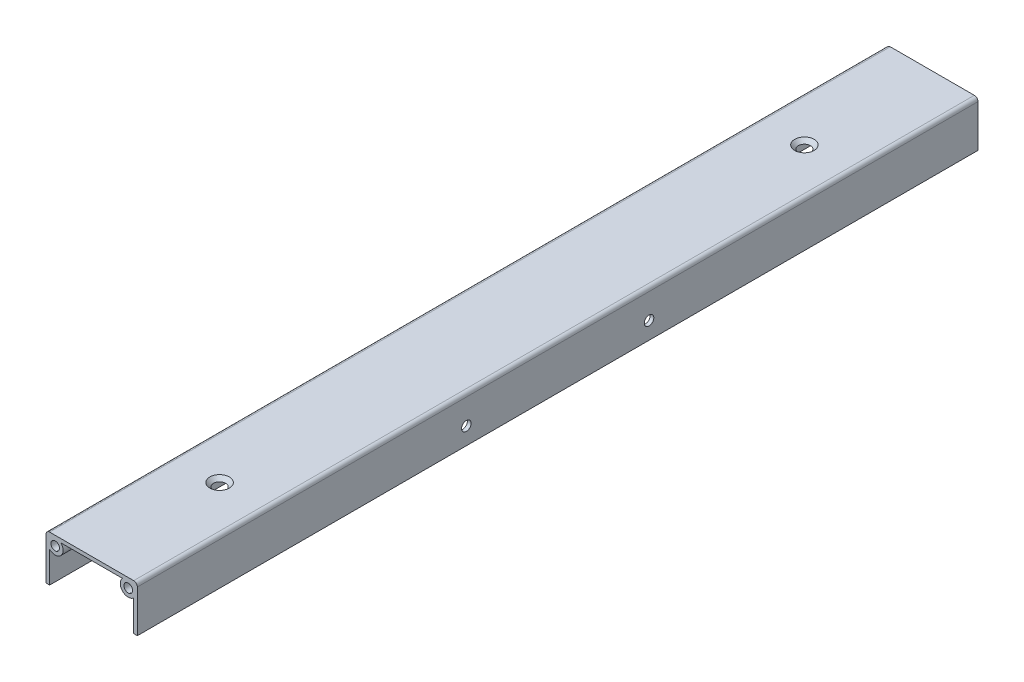
SolidWorks part; units mm, degrees
ref_plane "Front Plane" through (0, 0, 0) normal (0, 0, 1) x (1, 0, 0)
ref_plane "Top Plane" through (0, 0, 0) normal (0, 1, 0) x (1, 0, 0)
ref_plane "Right Plane" through (0, 0, 0) normal (1, 0, 0) x (0, 0, -1)
sketch "Sketch1" plane through (0, 0, 0) normal (0, 0, 1) x (1, 0, 0)
  line L0 (0, 31.75) -> (0, -31.75) construction
  line L1 (-31.75, -31.75) -> (31.75, -31.75)
  line L2 (-31.75, -31.75) -> (-31.75, 31.75)
  line L3 (-31.75, 31.75) -> (31.75, 31.75)
  line L4 (31.75, -31.75) -> (31.75, 31.75)
  line L5 (-31.75, -31.75) -> (31.75, 31.75) construction
  line L6 (-31.75, 31.75) -> (31.75, -31.75) construction
  line L7 (-31.75, 0) -> (31.75, 0) construction
  circle A0 centre (-25.4, 25.4) radius 3
  circle A1 centre (25.4, -25.4) radius 3
  circle A2 centre (-25.4, -25.4) radius 3
  circle A3 centre (25.4, 25.4) radius 3
  point P0 (0, 0)
  dimension "D3" = 6
  dimension "D9" = 50.8
  dimension "D4" = 50.8
  dimension "D1" = 63.5
  dimension "D2" = 63.5
  dimension "D5" = 6.35
extrude "Boss-Extrude1" add sketch "Sketch1" along normal mid plane 584.2
fillet "Fillet1" radius 2.54 4 edges at (-31.75, -31.75, 0) (31.75, -31.75, 0) (-31.75, 31.75, 0) (31.75, 31.75, 0)
shell "Shell1" thickness 2.54 removed face at (-28.4, -25.4, -292.1) removed face at (0, 0, 292.1)
sketch "Sketch3" plane through (0, 0, 292.1) normal (0, 0, 1) x (1, 0, 0)
  line L1 (-31.75, 29.21) -> (-31.75, -29.21) construction
  line L2 (-31.75, -0.1289) -> (31.9153, -0.1289)
  line L3 (-31.75, -0.1289) -> (-31.75, -31.8789)
  line L4 (-31.75, -31.8789) -> (31.9153, -31.8789)
  line L5 (31.9153, -0.1289) -> (31.9153, -31.8789)
  dimension "D1" = 31.75
extrude "Cut-Extrude2" cut sketch "Sketch3" against normal through all
hole_wizard "CSK for M6 Hex Socket Countersunk Head Screw1" positions "Sketch9" profile "Sketch8" countersink size "M6" standard "Lanco STD" end condition through all
sketch "Sketch9" plane through (0, 31.75, 0) normal (0, 1, 0) x (1, 0, 0)
  line L0 (29.21, -292.1) -> (-29.21, -292.1) construction
  line L1 (21.3781, 292.1) -> (-21.3781, 292.1) construction
  point P0 (0, 203.2)
  point P2 (0, -203.2)
  point P7 (0, 292.1)
  dimension "D1" = 88.9
  dimension "D2" = 88.9
sketch "Sketch8" plane through (0, 31.75, -203.2) normal (1, 0, 0) x (0, 0, 1)
  line L0 (0, 0) -> (0, 31.8789)
  line L1 (0, 31.8789) -> (3.2, 31.8789)
  line L2 (3.2, 31.8789) -> (3.2, 3.55)
  line L3 (3.2, 3.55) -> (6.75, 0)
  line L5 (6.75, 0) -> (0, 0)
  line L6 (-3.2, 3.55) -> (-6.75, 0) construction
  line L11 (0, -6.35) -> (0, 107.95) construction
  dimension "Thru Hole Dia." = 6.4
  dimension "Thru Hole Depth" = 31.8789
  dimension "Near C'Sink Dia." = 13.5
  dimension "Near C'Sink Angle" = 90
hole_wizard "M6 Clearance Hole1" positions "Sketch12" profile "Sketch11" hole size "M6" standard "ANSI Metric" end condition up to next
sketch "Sketch12" plane through (31.75, 0, 0) normal (1, 0, 0) x (0, 0, -1)
  line L0 (0, -50.1774) -> (0, 74.3545) construction
  line L2 (-292.1, -0.1289) -> (292.1, -0.1289) construction
  point P0 (63.5, 11.8118)
  point P2 (-63.5, 11.8118)
  dimension "D1" = 63.5
  dimension "D2" = 63.5
  dimension "D3" = 11.9407
sketch "Sketch11" plane through (31.75, 11.8118, -63.5) normal (0, 1, 0) x (0, 0, -1)
  line L0 (0, 0) -> (0, 2.54)
  line L1 (0, 2.54) -> (3.3, 2.54)
  line L2 (3.3, 2.54) -> (3.3, 0)
  line L5 (3.3, 0) -> (0, 0)
  line L11 (0, -6.35) -> (0, 107.95) construction
  dimension "Thru Hole Dia." = 6.6
  dimension "Thru Hole Depth" = 2.54
equation "\"D1@Boss-Extrude1\" = \"robot_width@Chassis.SLDASM\" - 6in"
